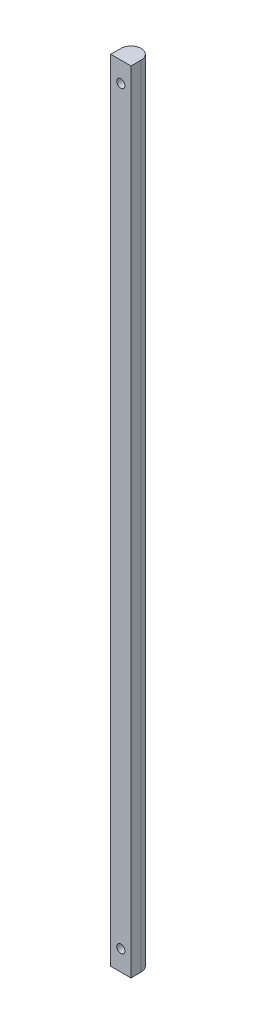
SolidWorks part; units mm, degrees
material "6061-T6 (SS)"
ref_plane "Front Plane" through (0, 0, 0) normal (0, 0, 1) x (1, 0, 0)
ref_plane "Top Plane" through (0, 0, 0) normal (0, 1, 0) x (1, 0, 0)
ref_plane "Right Plane" through (0, 0, 0) normal (1, 0, 0) x (0, 0, -1)
sketch "Sketch1" plane through (0, 0, 0) normal (0, 1, 0) x (1, 0, 0)
  line L0 (-3.175, 3.175) -> (-3.175, 0)
  line L1 (-3.175, 0) -> (3.175, 0)
  line L2 (3.175, 0) -> (3.175, 3.175)
  arc A0 (-3.175, 3.175) -> (3.175, 3.175) centre (0, 3.175) cw
  point P5 (0, 0)
  point P8 (0, 6.35)
  dimension "D2" = 3.175
  dimension "D1" = 6.35
  dimension "D3" = 6.35
extrude "Boss-Extrude1" add sketch "Sketch1" along normal mid plane 247.65
hole_wizard "#5-40 Tapped Hole1" positions "Sketch2" profile "Sketch3" tap size "#5-40" standard "ANSI Inch" end condition through all
sketch "Sketch2" plane through (0, 0, 0) normal (0, 0, 1) x (1, 0, 0)
  line L0 (-3.175, -123.825) -> (3.175, -123.825) construction
  point P2 (0, -117.475)
  dimension "D1" = 6.35
sketch "Sketch3" plane through (0, -117.475, 0) normal (1, 0, 0) x (0, -1, 0)
  line L0 (0, 0) -> (0, 6.35)
  line L1 (0, 6.35) -> (1.289, 6.35)
  line L2 (1.289, 6.35) -> (1.289, 0)
  line L5 (1.289, 0) -> (0, 0)
  line L11 (0, -6.35) -> (0, 107.95) construction
  dimension "Thru Tap Drill Dia." = 2.5781
  dimension "Thru Tap Drill Depth" = 6.35
cosmetic thread "Hole Thread1"
mirror "Mirror1" about plane through (0, 0, 0) normal (0, 1, 0) of "#5-40 Tapped Hole1"
cosmetic thread "Hole Thread2"
